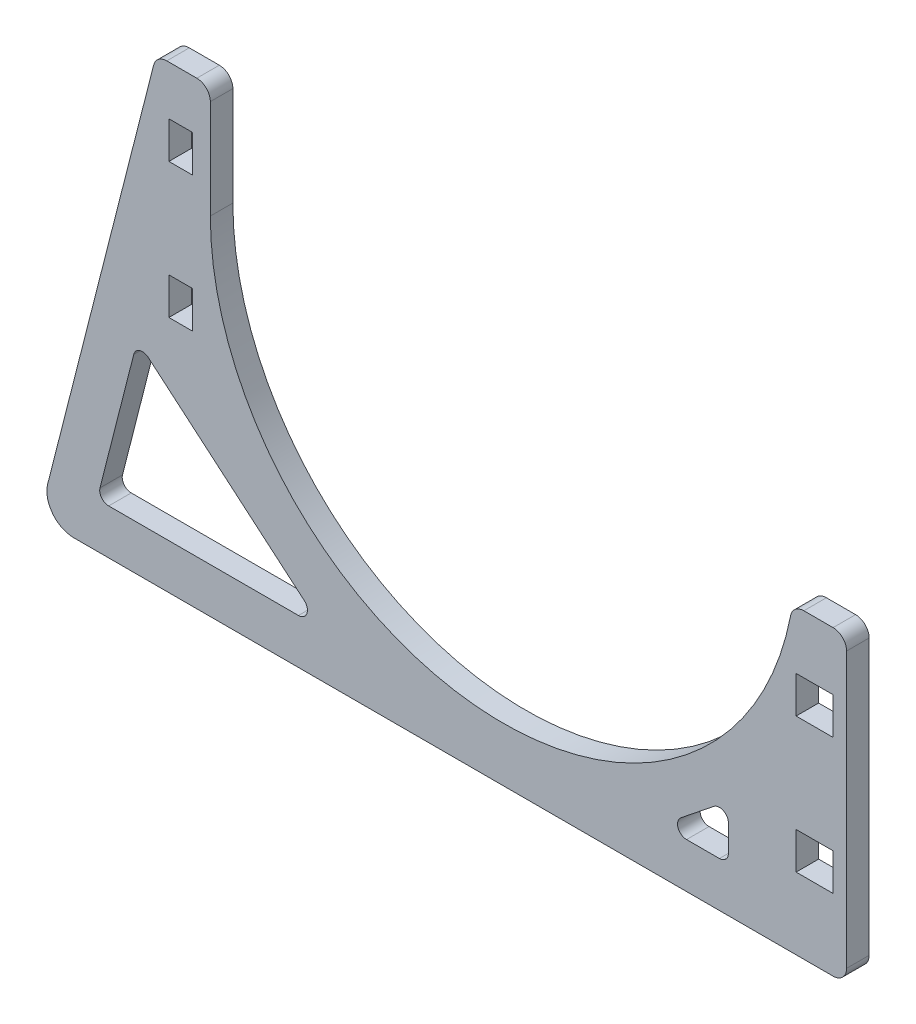
SolidWorks part; units mm, degrees
ref_plane "Alzado" through (0, 0, 0) normal (0, 0, 1) x (1, 0, 0)
ref_plane "Planta" through (0, 0, 0) normal (0, 1, 0) x (1, 0, 0)
ref_plane "Vista lateral" through (0, 0, 0) normal (1, 0, 0) x (0, 0, -1)
sketch "Croquis1" plane through (0, 0, 0) normal (0, 0, 1) x (1, 0, 0)
  line L0 (0, 0) -> (-179.2262, 0)
  line L1 (-179.2262, 0) -> (-153.2262, 102)
  line L2 (-153.2262, 102) -> (-141.2262, 102)
  line L3 (-141.2262, 102) -> (-141.2262, 77)
  line L4 (-12, 67) -> (0, 67)
  line L5 (0, 67) -> (0, 0)
  arc A0 (-141.2262, 77) -> (-12, 67) centre (-76.2262, 77) ccw
  point P8 (0, 0)
  point P12 (-140.0064, 75.3554)
  dimension "D1" = 65
  dimension "D2" = 12
  dimension "D3" = 10
  dimension "D4" = 25
  dimension "D5" = 12
  dimension "D6" = 38
  dimension "D7" = 77
extrude "Saliente-Extruir1" add sketch "Croquis1" along normal blind 5
ref_axis "Eje1" through (-76.2262, 77, 5) along (0, 0, -1)
sketch "Croquis4" plane through (0, 0, 5) normal (0, 0, 1) x (1, 0, 0)
  line L1 (-166.3574, 10) -> (-116.2262, 10)
  line L2 (-116.2262, 10) -> (-157.4358, 45)
  line L3 (-41.2262, 10) -> (-26.2262, 10)
  line L4 (-26.2262, 10) -> (-26.2262, 22)
  line L5 (-26.2262, 22) -> (-41.2262, 10)
  line L6 (-179.2262, 0) -> (0, 0) construction
  line L8 (-157.4358, 45) -> (-166.3574, 10)
  line L9 (-153.2262, 102) -> (-179.2262, 0) construction
  point P8 (-163.0374, 10)
  dimension "D1" = 10
  dimension "D2" = 35
  dimension "D3" = 10
  dimension "D4" = 35
  dimension "D5" = 40
  dimension "D6" = 15
  dimension "D7" = 12
extrude "Cortar-Extruir3" cut sketch "Croquis4" against normal blind 10
fillet "Redondeo4" radius 2 6 edges at (-116.2262, 10, 2.5) (-166.3574, 10, 2.5) (-157.4358, 45, 2.5) (-26.2262, 22, 2.5) (-26.2262, 10, 2.5) (-41.2262, 10, 2.5)
sketch "Croquis3" plane through (0, 0, 5) normal (0, 0, 1) x (1, 0, 0)
  line L0 (-141.2262, 77) -> (-141.2262, 102) construction
  line L1 (-150.4262, 91.1) -> (-145.2262, 91.1)
  line L2 (-150.4262, 91.1) -> (-150.4262, 82.9)
  line L3 (-150.4262, 82.9) -> (-145.2262, 82.9)
  line L4 (-145.2262, 91.1) -> (-145.2262, 82.9)
  line L5 (-141.2262, 102) -> (-153.2262, 102) construction
  line L6 (-150.4262, 61.1) -> (-145.2262, 61.1)
  line L7 (-150.4262, 61.1) -> (-150.4262, 52.9)
  line L8 (-150.4262, 52.9) -> (-145.2262, 52.9)
  line L9 (-145.2262, 61.1) -> (-145.2262, 52.9)
  point P6 (-145.2262, 87)
  point P13 (-145.2262, 57)
  dimension "D1" = 5.2
  dimension "D2" = 4
  dimension "D3" = 8.2
  dimension "D4" = 15
  dimension "D5" = 5.2
  dimension "D6" = 8.2
  dimension "D7" = 30
extrude "Cortar-Extruir2" cut sketch "Croquis3" against normal blind 10
fillet "Redondeo2" radius 3 5 edges at (-141.2262, 102, 2.5) (-153.2262, 102, 2.5) (0, 67, 2.5) (-12, 67, 2.5) (0, 0, 2.5)
fillet "Redondeo3" radius 6 1 edges at (-179.2262, 0, 2.5)
sketch "Croquis5" plane through (0, 0, 5) normal (0, 0, 1) x (1, 0, 0)
  line L0 (0, 3) -> (0, 64) construction
  line L1 (-11.2, 54.1) -> (-3, 54.1)
  line L2 (-11.2, 54.1) -> (-11.2, 45.9)
  line L3 (-11.2, 45.9) -> (-3, 45.9)
  line L4 (-3, 54.1) -> (-3, 45.9)
  line L5 (-11.2, 24.1) -> (-3, 24.1)
  line L6 (-11.2, 24.1) -> (-11.2, 15.9)
  line L7 (-11.2, 15.9) -> (-3, 15.9)
  line L8 (-3, 24.1) -> (-3, 15.9)
  line L9 (-171.5049, 0) -> (-3, 0) construction
  point P11 (-3, 50)
  point P12 (-3, 20)
  dimension "D1" = 8.2
  dimension "D2" = 3
  dimension "D3" = 8.2
  dimension "D4" = 8.2
  dimension "D5" = 8.2
  dimension "D6" = 30
  dimension "D7" = 20
extrude "Cortar-Extruir4" cut sketch "Croquis5" against normal blind 10
